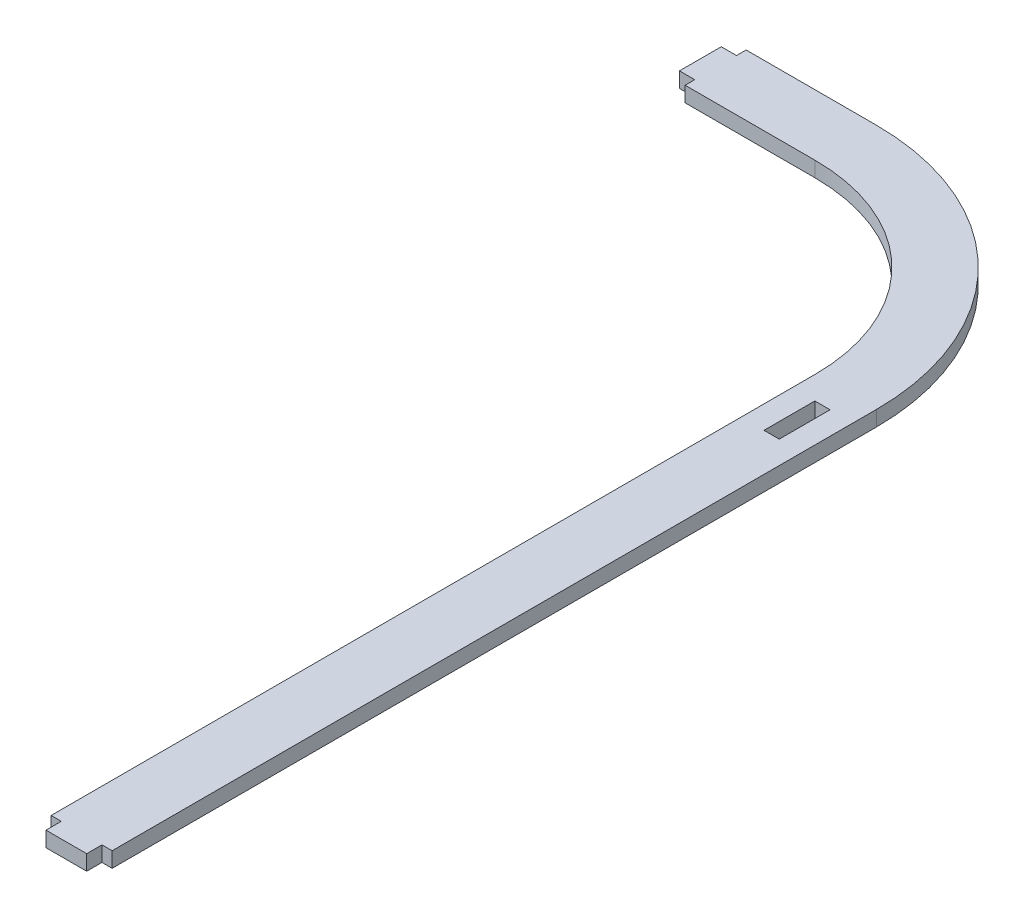
SolidWorks part; units mm, degrees
ref_plane "Alzado" through (0, 0, 0) normal (0, 0, 1) x (1, 0, 0)
ref_plane "Planta" through (0, 0, 0) normal (0, 1, 0) x (1, 0, 0)
ref_plane "Vista lateral" through (0, 0, 0) normal (1, 0, 0) x (0, 0, -1)
sketch "Croquis1" plane through (0, 0, 0) normal (0, 1, 0) x (1, 0, 0)
  line L0 (0, 0) -> (0, 8)
  line L1 (0, 8) -> (3, 8)
  line L2 (3, -2.107) -> (3, -0.2139)
  line L3 (3, 9.893) -> (28.5736, 9.893)
  line L5 (72.5, 3.893) -> (72.5, -188.737) construction
  line L6 (3, -2.107) -> (7.3583, -2.107)
  line L7 (0, -0.2139) -> (3, -0.2139)
  line L8 (0, 7.7861) -> (0, -0.2139)
  line L9 (3, 8) -> (3, 9.893)
  line L10 (65, -188.737) -> (67, -188.737)
  line L11 (77, -188.737) -> (77, -38.5334)
  line L12 (75, -191.737) -> (67, -191.737)
  line L13 (67, -191.737) -> (67, -188.737)
  line L14 (7.3583, -2.107) -> (28.5736, -2.107)
  line L15 (75, -191.737) -> (75, -188.737)
  line L16 (75, -188.737) -> (77, -188.737)
  line L17 (65, -117.737) -> (65, -188.737)
  line L19 (71, 3.893) -> (28.5736, -38.5334) construction
  line L20 (65, -117.737) -> (65, -38.5334)
  line L21 (71, -105.737) -> (71, 3.893) construction
  line L22 (77, -188.737) -> (77, -38.5334)
  line L23 (3, -2.107) -> (3, -191.737) construction
  arc A1 (65, -38.5334) -> (28.5736, -2.107) centre (28.5736, -38.5334) ccw
  arc A2 (77, -38.5334) -> (28.5736, 9.893) centre (28.5736, -38.5334) ccw
  dimension "D1" = 8
  dimension "D2" = 3
  dimension "D5" = 192.63
  dimension "D12" = 60
extrude "Saliente-Extruir1" add sketch "Croquis1" along normal blind 3 contours L22 L9 L1 L0 L8 L7 L2 L6 L14 L20 region at (2.1583, 0, -3.893)
sketch "Croquis2" plane through (0, 3, 0) normal (0, 1, 0) x (1, 0, 0)
  line L6 (71, -34.607) -> (71, -61.607) construction
  line L7 (69.5, -48.107) -> (69.5, -43.107)
  line L8 (69.5, -43.107) -> (72.5, -43.107)
  line L9 (72.5, -43.107) -> (72.5, -53.107)
  line L10 (72.5, -53.107) -> (69.5, -53.107)
  line L11 (69.5, -53.107) -> (69.5, -48.107)
  dimension "D4" = 5
  dimension "D5" = 3
  dimension "D6" = 10
extrude "Cortar-Extruir1" cut sketch "Croquis2" against normal blind 10
